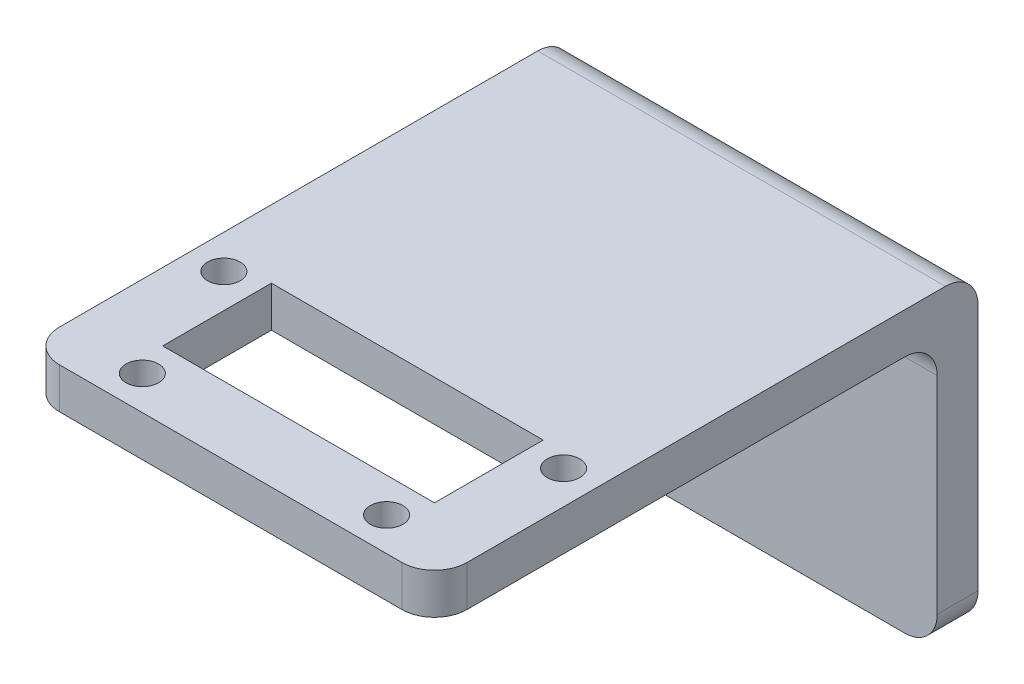
SolidWorks part; units mm, degrees
ref_plane "Plano frontal" through (0, 0, 0) normal (0, 0, 1) x (1, 0, 0)
ref_plane "Plano superior" through (0, 0, 0) normal (0, 1, 0) x (1, 0, 0)
ref_plane "Plano direito" through (0, 0, 0) normal (1, 0, 0) x (0, 0, -1)
sketch "Esboço1" plane through (0, 0, 0) normal (0, 1, 0) x (1, 0, 0)
  line L0 (0, 0) -> (0, 20) construction
  line L1 (-15, 20) -> (15, 20)
  line L2 (0, 0) -> (15, 0) construction
  line L3 (15, -20) -> (15, 20)
  line L4 (-15, 20) -> (-15, -20)
  line L5 (-15, -20) -> (15, -20)
  point P5 (0, 20)
  point P10 (15, 0)
  dimension "D1" = 30
  dimension "D2" = 40
extrude "Ressalto-extrusão1" add sketch "Esboço1" along normal blind 3
sketch "Esboço2" plane through (0, 3, 0) normal (0, 1, 0) x (1, 0, 0)
  line L4 (0, -20) -> (0, 20) construction
  line L5 (-15, -20) -> (15, -20) construction
  line L6 (15, 20) -> (-15, 20) construction
  line L7 (-10, -7) -> (10, -7)
  line L9 (-8.8957, -8) -> (9.1043, -8) construction
  line L10 (10, -7) -> (10, -15)
  line L11 (10, -15) -> (-10, -15)
  line L12 (-10, -15) -> (-10, -7)
  point P3 (0, -7)
  dimension "D1" = 0
  dimension "D2" = 20
  dimension "D3" = 1
  dimension "D4" = 8
extrude "Corte-extrusão1" cut sketch "Esboço2" against normal through all
sketch "Esboço3" plane through (0, 0, 0) normal (0, -1, 0) x (1, 0, 0)
  line L0 (-15, -20) -> (-15, 20) construction
  line L1 (-15, 20) -> (15, 20) construction
  line L3 (0, 20) -> (0.0283, 5) construction
  line L4 (-15.9979, 5) -> (16.0545, 5) construction
  line L5 (54.6527, 5) -> (-54.4441, 5) construction
  circle A0 centre (-9, 17.5) radius 1.2
  circle A2 centre (-12.5, 8) radius 1.2
  circle A4 centre (12.5451, 8.0472) radius 1.2
  circle A5 centre (9.0094, 17.5339) radius 1.2
  dimension "D1" = 2.4
  dimension "D7" = 2.4
  dimension "D2" = 6
  dimension "D3" = 2.5
  dimension "D9" = 2.5
  dimension "D11" = 3
extrude "Corte-extrusão2" cut sketch "Esboço3" against normal through all
sketch "Esboço4" plane through (0, 0, 0) normal (0, -1, 0) x (1, 0, 0)
  line L0 (-15, -17) -> (15, -17)
  line L4 (-15, 20) -> (-15, -20)
  line L5 (-15, -20) -> (15, -20)
  line L6 (15, -20) -> (15, 20)
  line L7 (15, 20) -> (-15, 20)
  line L8 (-15, 20) -> (-15, -20)
  line L9 (-15, -20) -> (15, -20)
  line L10 (15, -20) -> (15, 20)
  line L11 (15, 20) -> (-15, 20)
  line M18 (-15, 20) -> (-15, -20)
  line M20 (-15, -20) -> (15, -20)
  line M22 (15, -20) -> (15, 20)
  dimension "D2" = 3
  dimension "D1" = 0
extrude "Ressalto-extrusão2" add sketch "Esboço4" along normal blind 20 contours L0 M18 M20 M22 region at (0, 0, -18.5)
fillet "Filete5" radius 2.4 1 edges at (0, 0, -17)
fillet "Filete6" radius 2.4 1 edges at (0, 3, -20) tangent propagation no
fillet "Filete7" radius 2.4 2 edges at (15, 1.5, 20) (-15, 1.5, 20)
fillet "Filete8" radius 2.4 2 edges at (15, -20, -18.5) (-15, -20, -18.5)
